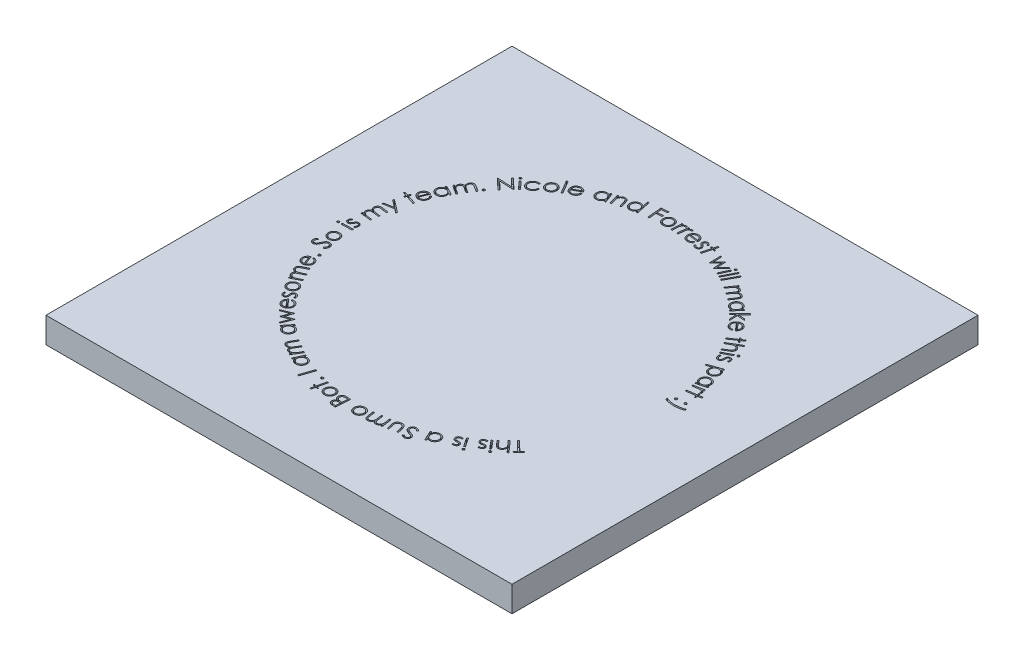
SolidWorks part; units mm, degrees
ref_plane "Front Plane" through (0, 0, 0) normal (0, 0, 1) x (1, 0, 0)
ref_plane "Top Plane" through (0, 0, 0) normal (0, 1, 0) x (1, 0, 0)
ref_plane "Right Plane" through (0, 0, 0) normal (1, 0, 0) x (0, 0, -1)
sketch "Sketch1" plane through (0, 0, 0) normal (0, 1, 0) x (1, 0, 0)
  line L1 (-50.8, -50.8) -> (50.8, -50.8)
  line L2 (-50.8, -50.8) -> (-50.8, 50.8)
  line L3 (-50.8, 50.8) -> (50.8, 50.8)
  line L4 (50.8, -50.8) -> (50.8, 50.8)
  line L5 (-50.8, -50.8) -> (50.8, 50.8) construction
  line L6 (-50.8, 50.8) -> (50.8, -50.8) construction
  point P0 (0, 0)
  dimension "D1" = 101.6
  dimension "D2" = 101.6
extrude "Boss-Extrude1" add sketch "Sketch1" along normal blind 5.588
sketch "Sketch2" plane through (0, 5.588, 0) normal (0, 1, 0) x (1, 0, 0)
  circle A1 centre (0, 0) radius 33.5395 construction
  text T0 "This is a Sumo Bot. I am awesome. So is my team. Nicole and Forrest will make this part :)"
extrude "Cut-Extrude2" cut sketch "Sketch2" against normal blind 1.27
